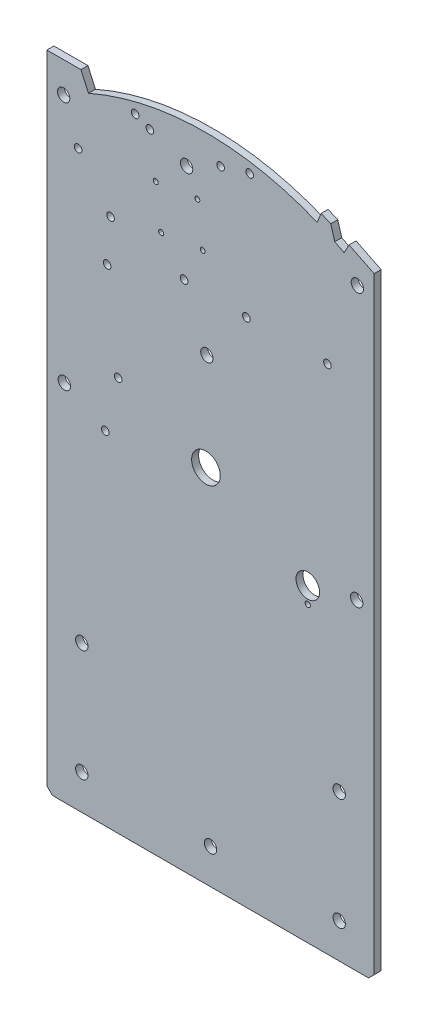
SolidWorks part; units mm, degrees
material "6061-T6 (SS)"
ref_plane "Front Plane" through (0, 0, 0) normal (0, 0, 1) x (1, 0, 0)
ref_plane "Top Plane" through (0, 0, 0) normal (0, 1, 0) x (1, 0, 0)
ref_plane "Right Plane" through (0, 0, 0) normal (1, 0, 0) x (0, 0, -1)
sketch "Sketch1" plane through (0, 0, 0) normal (0, 0, 1) x (1, 0, 0)
  line L0 (-37.0142, -65.193) -> (-37.0142, -242.993)
  line L1 (111.7057, -78.8372) -> (111.7057, -242.993)
  line L2 (111.7057, -242.993) -> (-37.0142, -242.993)
  line L3 (-28.4308, -65.1684) -> (-21.4969, -65.1485)
  line L4 (-21.4969, -65.1485) -> (-20.0556, -68.4088)
  line L41 (111.7057, -78.8372) -> (100.3159, -73.2191)
  line L42 (100.3159, -73.2191) -> (98.0489, -77.4075)
  line L43 (93.8204, -75.2164) -> (91.992, -69.0732)
  line L44 (91.992, -69.0732) -> (87.6255, -67.1718)
  line L45 (87.6255, -67.1718) -> (85.8005, -71.5708)
  line L46 (-18.13, -72.7646) -> (-20.0556, -68.4088)
  line L47 (-25.8634, -70.9762) -> (-28.4308, -65.1684) construction
  line L48 (-28.4308, -65.1684) -> (-37.0142, -65.193)
  line L75 (-20.0556, -68.4088) -> (-25.8634, -70.9762) construction
  arc A5 (98.0489, -77.4075) -> (93.8204, -75.2164) centre (35.2286, -193.468) ccw
  arc A9 (85.8005, -71.5708) -> (-18.13, -72.7646) centre (35.2286, -193.468) ccw
  dimension "D2" = 177.8
  dimension "D1" = 148.72
extrude "Boss-Extrude1" add sketch "Sketch1" against normal blind 3.175
sketch "Sketch2" plane through (0, 0, 0) normal (0, 0, 1) x (1, 0, 0)
  line L0 (111.7057, -231.472) -> (111.7057, -78.8372) construction
  line L1 (-21.4969, -65.1485) -> (-37.0142, -65.193) construction
  circle A0 centre (35.2684, -193.372) radius 6.5088
  dimension "D1" = 13.0175
  dimension "D2" = 76.4373
  dimension "D3" = 128.3861
extrude "Cut-Extrude1" cut sketch "Sketch2" against normal through all
hole_wizard "#4 Clearance Hole1" positions "Sketch4" profile "Sketch3" hole size "#4" standard "ANSI Inch" end condition through all
sketch "Sketch4" plane through (0, 0, 0) normal (0, 0, 1) x (1, 0, 0)
  point P0 (41.9398, -71.4888)
  point P3 (9.7895, -73.0113)
  point P6 (90.4886, -124.9671)
  point P9 (53.6587, -125.0729)
  point P12 (25.3388, -124.3417)
  point P15 (-9.6344, -135.8882)
  point P19 (55.1452, -67.7003)
  point P23 (3.102, -70.2707)
sketch "Sketch3" plane through (41.9398, -71.4888, 0) normal (1, 0, 0) x (0, -1, 0)
  line L0 (0, 0) -> (0, 3.175)
  line L1 (0, 3.175) -> (1.7272, 3.175)
  line L2 (1.7272, 3.175) -> (1.7272, 0)
  line L5 (1.7272, 0) -> (0, 0)
  line L11 (0, -6.35) -> (0, 107.95) construction
  dimension "Thru Hole Dia." = 3.4544
  dimension "Thru Hole Depth" = 3.175
hole_wizard "#10 Clearance Hole1" positions "Sketch6" profile "Sketch5" hole size "#10" standard "ANSI Inch" end condition through all
sketch "Sketch6" plane through (0, 0, 0) normal (0, 0, 1) x (1, 0, 0)
  point P0 (-29.3942, -79.072)
  point P3 (104.0857, -87.327)
  point P9 (35.696, -148.922)
  point P12 (26.4858, -79.072)
sketch "Sketch5" plane through (-29.3942, -79.072, 0) normal (1, 0, 0) x (0, -1, 0)
  line L0 (0, 0) -> (0, 3.175)
  line L1 (0, 3.175) -> (2.8067, 3.175)
  line L2 (2.8067, 3.175) -> (2.8067, 0)
  line L5 (2.8067, 0) -> (0, 0)
  line L11 (0, -6.35) -> (0, 107.95) construction
  dimension "Thru Hole Dia." = 5.6134
  dimension "Thru Hole Depth" = 3.175
hole_wizard "#4 Clearance Hole2" positions "Sketch8" profile "Sketch7" hole size "#4" standard "ANSI Inch" end condition through all
sketch "Sketch8" plane through (0, 0, 0) normal (0, 0, 1) x (1, 0, 0)
  point P0 (-8.0737, -116.3194)
  point P3 (-22.8122, -96.7821)
  point P12 (-10.4786, -201.738)
  point P15 (-4.604, -177.9805)
sketch "Sketch7" plane through (-8.0737, -116.3194, 0) normal (1, 0, 0) x (0, -1, 0)
  line L0 (0, 0) -> (0, 3.175)
  line L1 (0, 3.175) -> (1.7272, 3.175)
  line L2 (1.7272, 3.175) -> (1.7272, 0)
  line L5 (1.7272, 0) -> (0, 0)
  line L11 (0, -6.35) -> (0, 107.95) construction
  dimension "Thru Hole Dia." = 3.4544
  dimension "Thru Hole Depth" = 3.175
hole_wizard "27/64 (0.42188) Diameter Hole1" positions "Sketch10" profile "Sketch9" hole size "27/64" standard "ANSI Inch" end condition through all
sketch "Sketch10" plane through (0, 0, 0) normal (0, 0, 1) x (1, 0, 0)
  point P0 (81.5512, -216.6701)
sketch "Sketch9" plane through (81.5512, -216.6701, 0) normal (1, 0, 0) x (0, -1, 0)
  line L0 (0, 0) -> (0, 3.175)
  line L1 (0, 3.175) -> (5.3579, 3.175)
  line L2 (5.3579, 3.175) -> (5.3579, 0)
  line L5 (5.3579, 0) -> (0, 0)
  line L11 (0, -6.35) -> (0, 107.95) construction
  dimension "Thru Hole Dia." = 10.7158
  dimension "Thru Hole Depth" = 3.175
hole_wizard "3/32 (0.09375) Diameter Hole1" positions "Sketch12" profile "Sketch11" hole size "3/32" standard "ANSI Inch" end condition through all
sketch "Sketch12" plane through (0, 0, 0) normal (0, 0, 1) x (1, 0, 0)
  circle A0 centre (81.5512, -216.6701) radius 5.3579 construction
  point P0 (81.5512, -224.0361)
  dimension "D1" = 7.366
sketch "Sketch11" plane through (81.5512, -224.0361, 0) normal (1, 0, 0) x (0, -1, 0)
  line L0 (0, 0) -> (0, 3.175)
  line L1 (0, 3.175) -> (1.1906, 3.175)
  line L2 (1.1906, 3.175) -> (1.1906, 0)
  line L5 (1.1906, 0) -> (0, 0)
  line L11 (0, -6.35) -> (0, 107.95) construction
  dimension "Thru Hole Dia." = 2.3812
  dimension "Thru Hole Depth" = 3.175
hole_wizard "#10 Clearance Hole2" positions "Sketch14" profile "Sketch13" hole size "#10" standard "ANSI Inch" end condition through all
sketch "Sketch14" plane through (0, 0, 0) normal (0, 0, 1) x (1, 0, 0)
  circle A0 centre (-29.0767, -192.193) radius 2.8067 construction
  circle A1 centre (103.7682, -211.243) radius 2.8067 construction
  point P0 (-29.0767, -192.193)
  point P6 (103.7682, -211.243)
sketch "Sketch13" plane through (-29.0767, -192.193, 0) normal (1, 0, 0) x (0, -1, 0)
  line L0 (0, 0) -> (0, 3.175)
  line L1 (0, 3.175) -> (2.8067, 3.175)
  line L2 (2.8067, 3.175) -> (2.8067, 0)
  line L5 (2.8067, 0) -> (0, 0)
  line L11 (0, -6.35) -> (0, 107.95) construction
  dimension "Thru Hole Dia." = 5.6134
  dimension "Thru Hole Depth" = 3.175
sketch "Sketch15" plane through (0, 0, 0) normal (0, 0, 1) x (1, 0, 0)
  line L0 (109.1657, -357.293) -> (-34.4742, -357.293) construction
  line L1 (-37.0142, -242.993) -> (111.7057, -242.993)
  line L2 (-37.0142, -242.993) -> (-37.0142, -357.293)
  line L3 (-37.0142, -357.293) -> (111.7057, -357.293)
  line L4 (111.7057, -242.993) -> (111.7057, -357.293)
extrude "Boss-Extrude2" add sketch "Sketch15" against normal through all
chamfer "Chamfer1" distance 2.54 angle 45 2 edges at (-37.0142, -357.293, -1.5875) (111.7057, -357.293, -1.5875)
hole_wizard "#10 Clearance Hole3" positions "Sketch16" profile "Sketch17" hole size "#10" standard "ANSI Inch" end condition through all
sketch "Sketch16" plane through (0, 0, 0) normal (0, 0, 1) x (1, 0, 0)
  point P0 (95.8307, -341.418)
  point P3 (37.3457, -341.418)
  point P6 (-21.1392, -341.418)
  point P9 (95.8307, -290.618)
  point P12 (-21.1392, -290.618)
sketch "Sketch17" plane through (95.8307, -341.418, 0) normal (1, 0, 0) x (0, -1, 0)
  line L0 (0, 0) -> (0, 3.175)
  line L1 (0, 3.175) -> (2.8067, 3.175)
  line L2 (2.8067, 3.175) -> (2.8067, 0)
  line L5 (2.8067, 0) -> (0, 0)
  line L11 (0, -6.35) -> (0, 107.95) construction
  dimension "Thru Hole Dia." = 5.6134
  dimension "Thru Hole Depth" = 3.175
hole_wizard "#4-40 Tapped Hole1" positions "Sketch20" profile "Sketch21" tap size "#4-40" standard "ANSI Inch" end condition through all
sketch "Sketch20" plane through (0, 0, 0) normal (0, 0, 1) x (1, 0, 0)
  point P7 (31.3544, -89.7014)
  point P10 (12.4643, -92.1648)
  point P13 (14.9278, -111.0549)
  point P16 (33.8178, -108.5914)
sketch "Sketch21" plane through (31.3544, -89.7014, 0) normal (1, 0, 0) x (0, -1, 0)
  line L0 (0, 0) -> (0, 3.175)
  line L1 (0, 3.175) -> (1.1303, 3.175)
  line L2 (1.1303, 3.175) -> (1.1303, 0)
  line L5 (1.1303, 0) -> (0, 0)
  line L11 (0, -6.35) -> (0, 107.95) construction
  dimension "Thru Tap Drill Dia." = 2.2606
  dimension "Thru Tap Drill Depth" = 3.175
cosmetic thread "Hole Thread1" parameters "D2"=2.8448
cosmetic thread "Hole Thread2" parameters "D2"=2.8448
cosmetic thread "Hole Thread3" parameters "D2"=2.8448
cosmetic thread "Hole Thread4" parameters "D2"=2.8448
